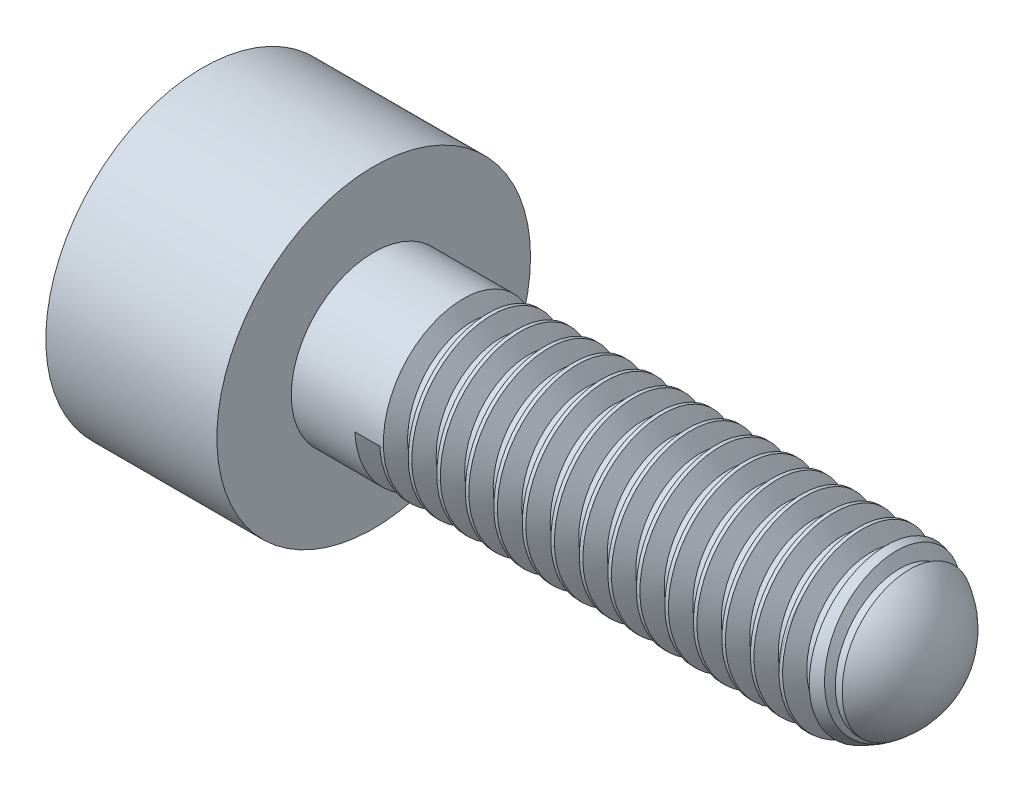
SolidWorks part; units mm, degrees
material "AISI 304"
ref_plane "Front Plane" through (0, 0, 0) normal (0, 0, 1) x (1, 0, 0)
ref_plane "Top Plane" through (0, 0, 0) normal (0, 1, 0) x (1, 0, 0)
ref_plane "Right Plane" through (0, 0, 0) normal (1, 0, 0) x (0, 0, -1)
sketch "Sketch1" plane through (0, 0, 0) normal (1, 0, 0) x (0, 0, -1)
  circle A0 centre (0, 0) radius 1.446
  circle A1 centre (0, 0) radius 2.75
  dimension "D1" = 2.892
  dimension "D2" = 5.5
extrude "Boss-Extrude1" add sketch "Sketch1" along normal blind 10 contours A0
extrude "Boss-Extrude2" add sketch "Sketch1<3>" against normal blind 3 contours A1
sketch "Sketch1<3>" plane through (0, 0, 0) normal (1, 0, 0) x (0, 0, -1) same geometry as "Sketch1"
fillet "Fillet1" radius 1.446 1 edges at (10, 0, -1.446)
sketch "Sketch2" plane through (-3, 0, 0) normal (-1, 0, 0) x (0, 0, 1)
  line L1 (1.3437, -1.093) -> (1.6184, 0.6172)
  line L2 (1.6184, 0.6172) -> (0.2747, 1.7101)
  line L3 (0.2747, 1.7101) -> (-1.3437, 1.093)
  line L4 (-1.3437, 1.093) -> (-1.6184, -0.6172)
  line L5 (-1.6184, -0.6172) -> (-0.2747, -1.7101)
  line L6 (-0.2747, -1.7101) -> (1.3437, -1.093)
  circle A0 centre (0, 0) radius 1.5 construction
  dimension "D1" = 1.5
extrude "Cut-Extrude1" cut sketch "Sketch2" against normal blind 1.5
thread "Thread1" pitch 0.5 method cut profile "Thread Profile1" start angle 0, offset 2, length 9, pitch 0.5, diameter 2.892
ref_plane "Plane1" through (10.554, 0, 1.446) normal (0, -1, 0) x (0, 0, 1)
sketch "Thread Profile1" plane through (10.554, 0, 1.446) normal (0, -1, 0) x (0, 0, 1)
  line L0 (0, 0) -> (0, 0.5) construction
  line L11 (0, 0) -> (0, 0.4375)
  line L12 (0, 0.4375) -> (-0.2706, 0.2812)
  line L13 (-0.2706, 0.2812) -> (-0.2706, 0.1562)
  line L15 (-0.2706, 0.1562) -> (0, 0)
  line L17 (-0.2706, 0.2187) -> (0, 0.2187) construction
  point P2 (0, 0)
  dimension "Pitch" = 0.5
  dimension "Profile_Angle" = 60
  dimension "Profile_Land" = 0.125
  dimension "Profile_Height" = 0.2706
